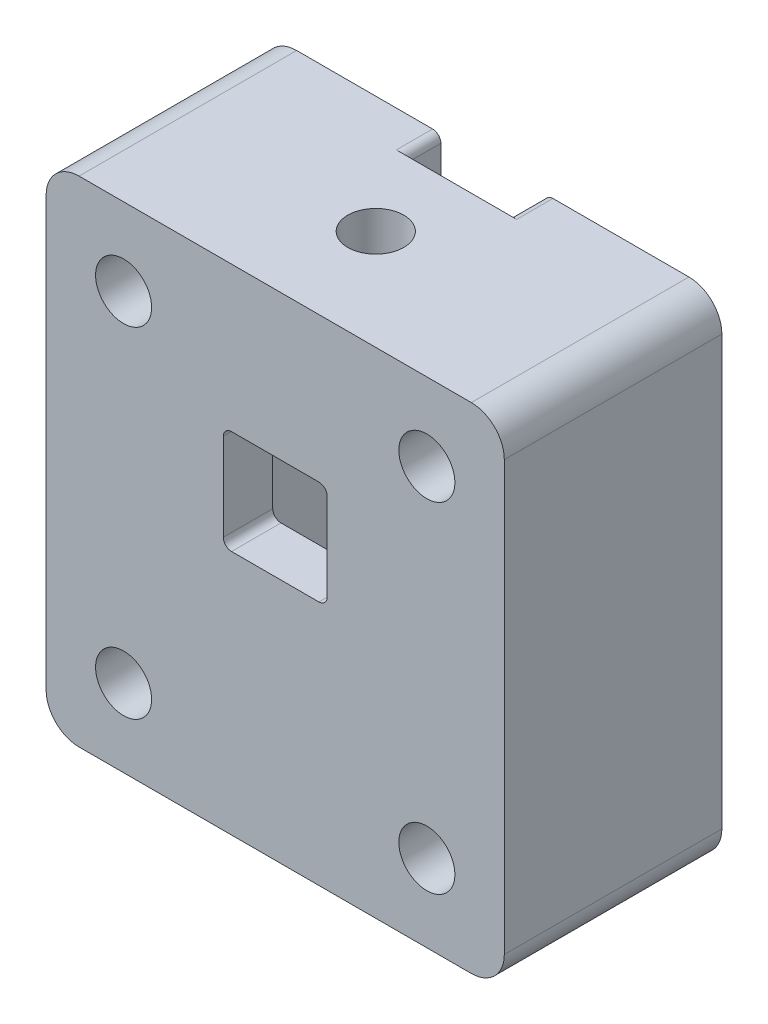
SolidWorks part; units mm, degrees
ref_plane "Front" through (0, 0, 0) normal (0, 0, 1) x (1, 0, 0)
ref_plane "Top" through (0, 0, 0) normal (0, 1, 0) x (1, 0, 0)
ref_plane "Right" through (0, 0, 0) normal (1, 0, 0) x (0, 0, -1)
sketch "Sketch2" plane through (0, 0, 0) normal (0, 1, 0) x (1, 0, 0)
  line L0 (0, -50) -> (0, 50) construction
  line L1 (-13.9, -6.6) -> (13.9, -6.6)
  line L2 (-13.9, -6.6) -> (-13.9, 6.6)
  line L3 (-13.9, 6.6) -> (13.9, 6.6)
  line L4 (13.9, -6.6) -> (13.9, 6.6)
  line L5 (-13.9, -6.6) -> (13.9, 6.6) construction
  line L6 (-13.9, 6.6) -> (13.9, -6.6) construction
  point P0 (0, 0)
  dimension "D2" = 13.9
  dimension "D1" = 13.2
extrude "Boss-Extrude1" add sketch "Sketch2" along normal mid plane 30
sketch "Sketch7" plane through (0, 0, 6.6) normal (0, 0, 1) x (1, 0, 0)
  line L1 (-13.9, 15) -> (-13.9, -15) construction
  line L2 (-13.9, 15) -> (13.9, 15) construction
  circle A0 centre (-9.2, 10.3) radius 1.7
  point P8 (-9.2, 10.3)
  dimension "D3" = 3.4
  dimension "D1" = 4.7
  dimension "D2" = 4.7
extrude "Cut-Extrude1" cut sketch "Sketch7" against normal through all
mirror "Mirror1" about plane through (0, 0, 0) normal (1, 0, 0) of "Cut-Extrude1"
mirror "Mirror2" about plane through (0, 0, 0) normal (0, 1, 0) of "Mirror1"
sketch "Sketch8" plane through (0, -15, 0) normal (0, -1, 0) x (1, 0, 0)
  line L0 (0, -50) -> (0, 50) construction
  line L1 (-4.15, -6.6) -> (4.15, -6.6)
  line L2 (-4.15, -6.6) -> (-4.15, 3.6)
  line L3 (-4.15, 3.6) -> (4.15, 3.6)
  line L4 (4.15, -6.6) -> (4.15, 3.6)
  line L5 (-4.15, -6.6) -> (4.15, 3.6) construction
  line L6 (-4.15, 3.6) -> (4.15, -6.6) construction
  line L7 (13.9, -6.6) -> (-13.9, -6.6) construction
  point P0 (0, -1.5)
  dimension "D1" = 10.2
  dimension "D2" = 8.3
extrude "Cut-Extrude2" cut sketch "Sketch8" against normal blind 21.2
sketch "Sketch11" plane through (4.15, 0, 0) normal (-1, 0, 0) x (0, 0, 1)
  line L0 (-11.6, 15) -> (-4.4, 15)
  line L1 (-4.4, 15) -> (-4.4, 14.2)
  line L2 (-4.4, 14.2) -> (-3.8, 14.2)
  line L3 (-3.8, 14.2) -> (-3.8, 13)
  line L4 (-3.8, 13) -> (-4.4, 13)
  line L5 (-4.4, 13) -> (-4.4, 12.2)
  line L6 (-4.4, 12.2) -> (-3.8, 12.2)
  line L7 (-3.8, 12.2) -> (-3.8, 11)
  line L8 (-3.8, 11) -> (-4.4, 11)
  line L9 (-4.4, 11) -> (-4.4, 10.2)
  line L10 (-4.4, 10.2) -> (-3.8, 10.2)
  line L11 (-3.8, 10.2) -> (-3.8, 9)
  line L12 (-3.8, 9) -> (-4.4, 9)
  line L13 (-4.4, 9) -> (-4.4, 8.2)
  line L14 (-4.4, 8.2) -> (-3.8, 8.2)
  line L15 (-3.8, 8.2) -> (-3.8, 7)
  line L16 (-3.8, 7) -> (-4.4, 7)
  line L17 (-4.4, 7) -> (-4.4, 6.2)
  line L18 (-4.4, 6.2) -> (-11.6, 6.2)
  line L19 (-11.6, 6.2) -> (-11.6, 15)
  line L21 (-6.6, 6.2) -> (-6.6, -15) construction
  line L22 (-6.6, 6.2) -> (3.6, 6.2) construction
  line L23 (-11.6, 10.6) -> (-4.4, 10.6) construction
  point P24 (-6.6, 15)
  dimension "D4" = 2.2
  dimension "D5" = 5
extrude "Cut-Extrude5" cut sketch "Sketch11" along normal offset from surface (6.3 mm away) 1 from offset 1 up to face at (-4.15, -4.4, -1.5)
sketch "Sketch12" plane through (0, 0, 3.6) normal (0, 0, -1) x (-1, 0, 0)
  line L0 (0, 50) -> (0, -50) construction
  line L2 (-3.15, -0.1) -> (3.15, -0.1)
  line L3 (-3.15, -0.1) -> (-3.15, 6.2)
  line L4 (-3.15, 6.2) -> (3.15, 6.2)
  line L5 (3.15, -0.1) -> (3.15, 6.2)
  line L6 (-3.15, -0.1) -> (3.15, 6.2) construction
  line L7 (-3.15, 6.2) -> (3.15, -0.1) construction
  line L8 (4.15, 6.2) -> (4.15, -15) construction
  line L9 (-4.15, 6.2) -> (4.15, 6.2) construction
  point P2 (0, 3.05)
  dimension "D2" = 1
  dimension "D3" = 6.3
  dimension "D4" = 6.3
extrude "Cut-Extrude6" cut sketch "Sketch12" against normal through all
fillet "Fillet4" radius 0.5 4 edges at (-3.15, -0.1, 5.1) (-3.15, 6.2, 5.1) (3.15, -0.1, 5.1) (3.15, 6.2, 5.1)
fillet "Fillet3" radius 2 4 edges at (13.9, -15, 0) (13.9, 15, 0) (-13.9, -15, 0) (-13.9, 15, 0)
fillet "Fillet5" radius 0.5 6 edges at (-4.15, -15, -1.5) (4.15, -15, -1.5) (-3.15, 15, -5.5) (3.15, 15, -5.5) (-3.15, 6.2, -5.5) (3.15, 6.2, -5.5)
sketch "Sketch13" plane through (0, 6.2, 0) normal (0, -1, 0) x (1, 0, 0)
  line L0 (0, -50) -> (0, 50) construction
  line L2 (4.65, 3.6) -> (-4.65, 3.6) construction
  circle A0 centre (0, 0.5) radius 1.7
  dimension "D2" = 3.4
  dimension "D1" = 3.1
extrude "Cut-Extrude7" cut sketch "Sketch13" against normal through all
equation "\"M3_d\"= 3.4"
equation "\"linear_bearing_d\"= 12"
equation "\"linear_bearing_l\"= 30"
equation "\"D1@Boss-Extrude1\"= \"linear_bearing_l\""
equation "\"t\"= 3"
equation "\"D2@Sketch2\"= \"linear_bearing_d\" / 2 + \"t\" / 2 + \"M3_d\" + \"t\""
equation "\"D3@Sketch7\"= \"M3_d\""
equation "\"D1@Sketch7\"= \"M3_d\" / 2 + \"t\" "
equation "\"D2@Sketch7\"=\"D1@Sketch7\""
equation "\"groove_big_b\"= 8.2 + 0.1"
equation "\"D2@Sketch8\"=\"groove_big_b\""
equation "\"groove_small_l\"= 9 - 0.2"
equation "\"D1@Cut-Extrude2\"= \"linear_bearing_l\" - \"groove_small_l\""
equation "\"groove_small_b\"= 6.2 + 0.1"
equation "\"groove_h\"= 1.7 + 0.5"
equation "\"D4@Sketch11\"= \"groove_h\""
equation "\"tensioner_h\"= 7.8 + 0.2"
equation "\"D1@Sketch2\"= \"tensioner_h\" + \"groove_h\" + \"t\""
equation "\"D1@Sketch8\"=\"tensioner_h\" + \"groove_h\""
equation "\"D4@Sketch12\"= \"D3@Sketch12\""
equation "\"M3_nut_m_XY\"= 6.2"
equation "\"D2@Sketch13\"=\"M3_d\""
equation "\"D19@Cut-Extrude5\"=(\"groove_big_b\" - \"groove_small_b\") / 2"
equation "\"D1@Cut-Extrude5\"=(\"groove_big_b\" - \"groove_small_b\") / 2"
equation "\"D1@Sketch13\"=\"M3_nut_m_XY\" / 2"
